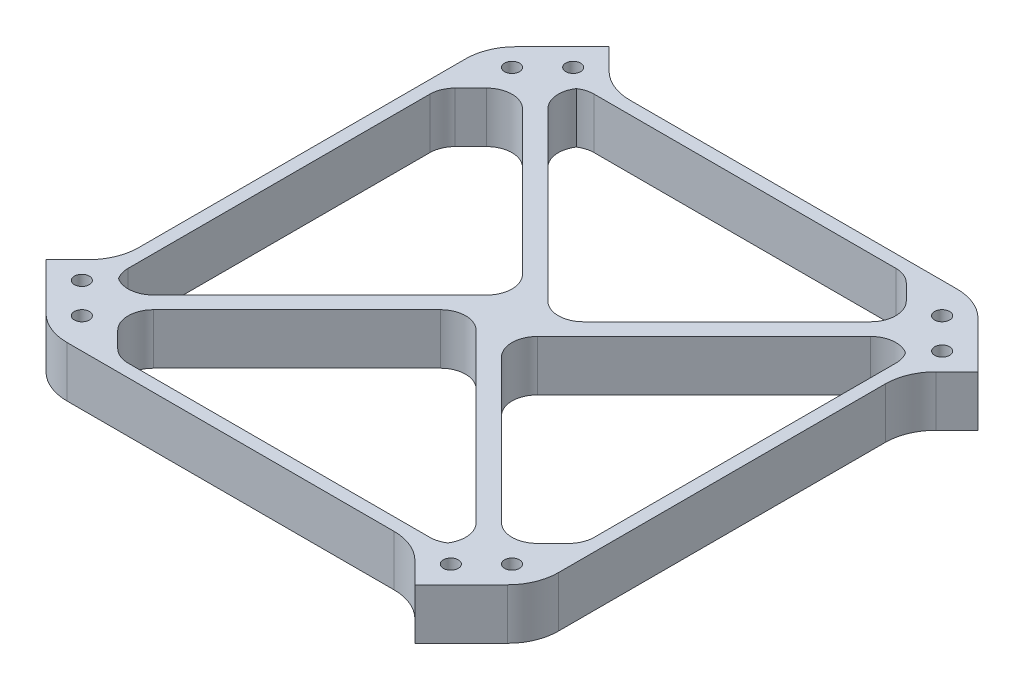
SolidWorks part; units mm, degrees
ref_plane "Front Plane" through (0, 0, 0) normal (0, 0, 1) x (1, 0, 0)
ref_plane "Top Plane" through (0, 0, 0) normal (0, 1, 0) x (1, 0, 0)
ref_plane "Right Plane" through (0, 0, 0) normal (1, 0, 0) x (0, 0, -1)
sketch "Sketch1" plane through (0, 0, 0) normal (0, 1, 0) x (1, 0, 0)
  line L0 (-55.533, 36.3909) -> (-36.3909, 55.533) construction
  line L1 (-36.3909, 55.533) -> (36.3909, 55.533) construction
  line L2 (36.3909, 55.533) -> (55.533, 36.3909) construction
  line L3 (55.533, 36.3909) -> (55.533, -36.3909) construction
  line L4 (55.533, -36.3909) -> (36.3909, -55.533) construction
  line L5 (36.3909, -55.533) -> (-36.3909, -55.533) construction
  line L6 (-36.3909, -55.533) -> (-55.533, -36.3909) construction
  line L7 (-55.533, -36.3909) -> (-55.533, 36.3909) construction
  line L8 (0, 0) -> (0, 31.0491) construction
  line L9 (0, 0) -> (32.6609, 0) construction
  line L10 (-48.4619, 43.4619) -> (-36.3909, 55.533)
  line L11 (-45.9619, -45.9619) -> (45.9619, -45.9619) construction
  line L12 (-45.9619, -45.9619) -> (-45.9619, 45.9619) construction
  line L13 (-45.9619, 45.9619) -> (45.9619, 45.9619) construction
  line L14 (45.9619, -45.9619) -> (45.9619, 45.9619) construction
  line L15 (-36.3909, 55.533) -> (-29.3198, 48.4619)
  line L16 (-29.3198, 48.4619) -> (43.4619, 48.4619)
  line L17 (43.4619, 48.4619) -> (55.533, 36.3909)
  line L18 (55.533, 36.3909) -> (48.4619, 29.3198)
  line L19 (48.4619, 29.3198) -> (48.4619, -43.4619)
  line L20 (48.4619, -43.4619) -> (36.3909, -55.533)
  line L21 (36.3909, -55.533) -> (29.3198, -48.4619)
  line L22 (29.3198, -48.4619) -> (-43.4619, -48.4619)
  line L23 (-43.4619, -48.4619) -> (-55.533, -36.3909)
  line L24 (-55.533, -36.3909) -> (-48.4619, -29.3198)
  line L25 (-48.4619, -29.3198) -> (-48.4619, 43.4619)
  point P10 (0, 0)
  point P18 (-45.9619, 45.9619)
  point P19 (0, 0)
  point P30 (0, 0)
  point P31 (0, 0)
  point P32 (0, 0)
  point P33 (0, 0)
  dimension "D1" = 65
  dimension "D2" = 10
  dimension "D3" = 2.5
extrude "Boss-Extrude1" add sketch "Sketch1" along normal blind 10
sketch "Sketch2" plane through (0, 10, 0) normal (0, 1, 0) x (1, 0, 0)
  line L0 (0, 0) -> (0, 27.7289) construction
  line L1 (48.4619, -48.4619) -> (-48.4619, -48.4619) construction
  line L2 (-48.4619, 43.4619) -> (-48.4619, -29.3198) construction
  line L3 (48.4619, 48.4619) -> (-48.4619, 48.4619) construction
  line L4 (-48.4619, -48.4619) -> (-48.4619, 48.4619) construction
  line L5 (0, 0) -> (26.129, 0) construction
  line L10 (-2.5, 4.5711) -> (-42.4264, -35.3553)
  line L11 (-45.9619, 31.8198) -> (-37.8553, 39.9264)
  line L12 (-37.8553, 39.9264) -> (-2.5, 4.5711)
  line L13 (-42.4264, -35.3553) -> (-45.9619, -31.8198)
  line L15 (43.4619, 48.4619) -> (-29.3198, 48.4619) construction
  line L16 (-43.4619, -48.4619) -> (29.3198, -48.4619) construction
  line L17 (48.4619, 48.4619) -> (48.4619, -48.4619) construction
  line L18 (48.4619, -43.4619) -> (48.4619, 29.3198) construction
  line L19 (-36.3909, 55.533) -> (-48.4619, 43.4619) construction
  line L20 (-45.9619, -31.8198) -> (-45.9619, 31.8198)
  line L21 (-48.4619, -29.3198) -> (-45.9619, -31.8198) construction
  dimension "D1" = 10
  dimension "D2" = 5
  dimension "D3" = 5
  dimension "D4" = 2.5
extrude "Cut-Extrude1" cut sketch "Sketch2" against normal through all
ref_axis "Axis2" through (0, 10.5, 0) along (0, -1, 0)
fillet "Fillet4" radius 5 5 edges at (-37.8553, 5, -39.9264) (-2.5, 5, -4.5711) (-45.9619, 5, 31.8198) (-42.4264, 5, 35.3553) (-45.9619, 5, -31.8198)
pattern_circular "CirPattern6" count 4 over 360 about axis through (0, 10.5, 0) along (0, -1, 0) of "Cut-Extrude1", "Fillet4"
fillet "Fillet5" radius 10 8 edges at (43.4619, 5, -48.4619) (-29.3198, 5, -48.4619) (-48.4619, 5, -43.4619) (-48.4619, 5, 29.3198) (-43.4619, 5, 48.4619) (29.3198, 5, 48.4619) (48.4619, 5, -29.3198) (48.4619, 5, 43.4619)
hole_wizard "#32 (0.116) Diameter Hole1" positions "Sketch3" profile "Sketch4" hole size "#32" standard "ANSI Inch" end condition through all
sketch "Sketch3" plane through (0, 10, 0) normal (0, 1, 0) x (1, 0, 0)
  line L1 (42.4264, -42.4264) -> (-42.4264, -42.4264) construction
  line L2 (42.4264, -42.4264) -> (42.4264, 42.4264) construction
  line L3 (42.4264, 42.4264) -> (-42.4264, 42.4264) construction
  line L4 (-42.4264, -42.4264) -> (-42.4264, 42.4264) construction
  line L5 (0, 0) -> (0, 27.9091) construction
  line L7 (0, 0) -> (26.5726, 0) construction
  line L9 (-36.3909, 55.533) -> (-45.533, 46.3909) construction
  line L11 (-43.4619, 48.4619) -> (-36.3909, 55.533) construction
  line L12 (-43.4619, 48.4619) -> (-36.3909, 41.3909) construction
  line L13 (-36.3909, 55.533) -> (-29.3198, 48.4619) construction
  line L16 (-36.3909, 41.3909) -> (-36.3909, 55.533) construction
  line L18 (-43.4619, 48.4619) -> (-29.3198, 48.4619) construction
  line L20 (-29.3198, 48.4619) -> (-36.3909, 41.3909) construction
  line L22 (-41.3909, 36.3909) -> (-44.4975, 33.2843) construction
  point P3 (-42.4264, 42.4264)
  point P355 (-36.3909, 48.4619)
  dimension "D1" = 5
  dimension "D2" = 60
sketch "Sketch4" plane through (-42.4264, 10, -42.4264) normal (1, 0, 0) x (0, 0, 1)
  line L0 (0, 0) -> (0, 10)
  line L1 (0, 10) -> (1.4732, 10)
  line L2 (1.4732, 10) -> (1.4732, 0)
  line L5 (1.4732, 0) -> (0, 0)
  line L11 (0, -6.35) -> (0, 107.95) construction
  dimension "Thru Hole Dia." = 2.9464
  dimension "Thru Hole Depth" = 10
pattern_circular "CirPattern7" count 4 over 360 about axis through (0, 10.5, 0) along (0, -1, 0) of "#32 (0.116) Diameter Hole1"
